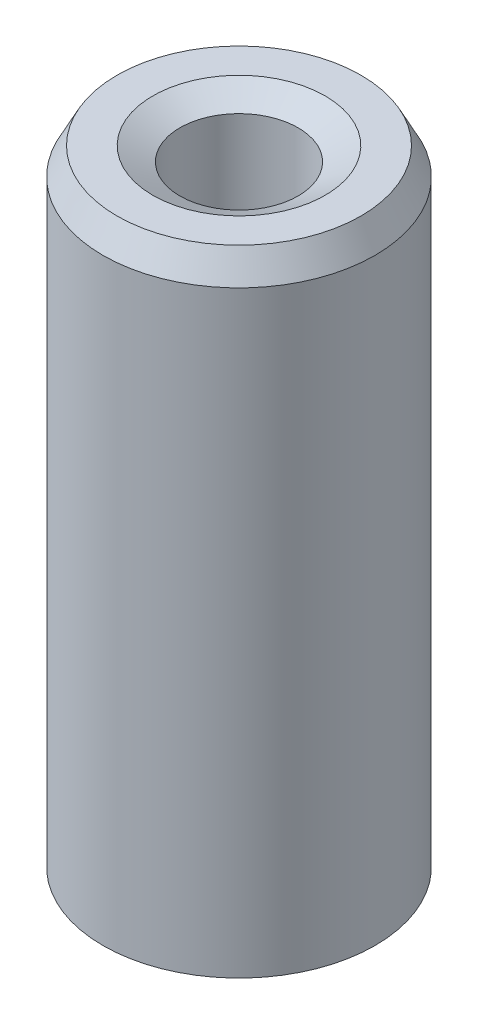
SolidWorks part; units mm, degrees
ref_plane "Front Plane" through (0, 0, 0) normal (0, 0, 1) x (1, 0, 0)
ref_plane "Top Plane" through (0, 0, 0) normal (0, 1, 0) x (1, 0, 0)
ref_plane "Right Plane" through (0, 0, 0) normal (1, 0, 0) x (0, 0, -1)
sketch "Sketch1" plane through (0, 0, 0) normal (0, 1, 0) x (1, 0, 0)
  circle A0 centre (0, 0) radius 15
  dimension "SLEEVE_OD" = 30
extrude "Boss-Extrude1" add sketch "Sketch1" along normal blind 70.4278
sketch "Sketch2" plane through (0, 0, 0) normal (0, 1, 0) x (1, 0, 0)
  circle A0 centre (0, 0) radius 6.5178
  dimension "BORE_D" = 13.0356
extrude "Cut-Extrude1" cut sketch "Sketch2" along normal through all
chamfer "Chamfer1" distance 2.9801 angle 27.527 4 edges at (0, 70.4278, 6.5178) (0, 0, 6.5178) (0, 0, 15) (0, 70.4278, 15) first distance on face at (0, 70.4278, 6.5178) first distance on face at (0, 0, 6.5178) first distance on face at (0, 70.4278, 15)
